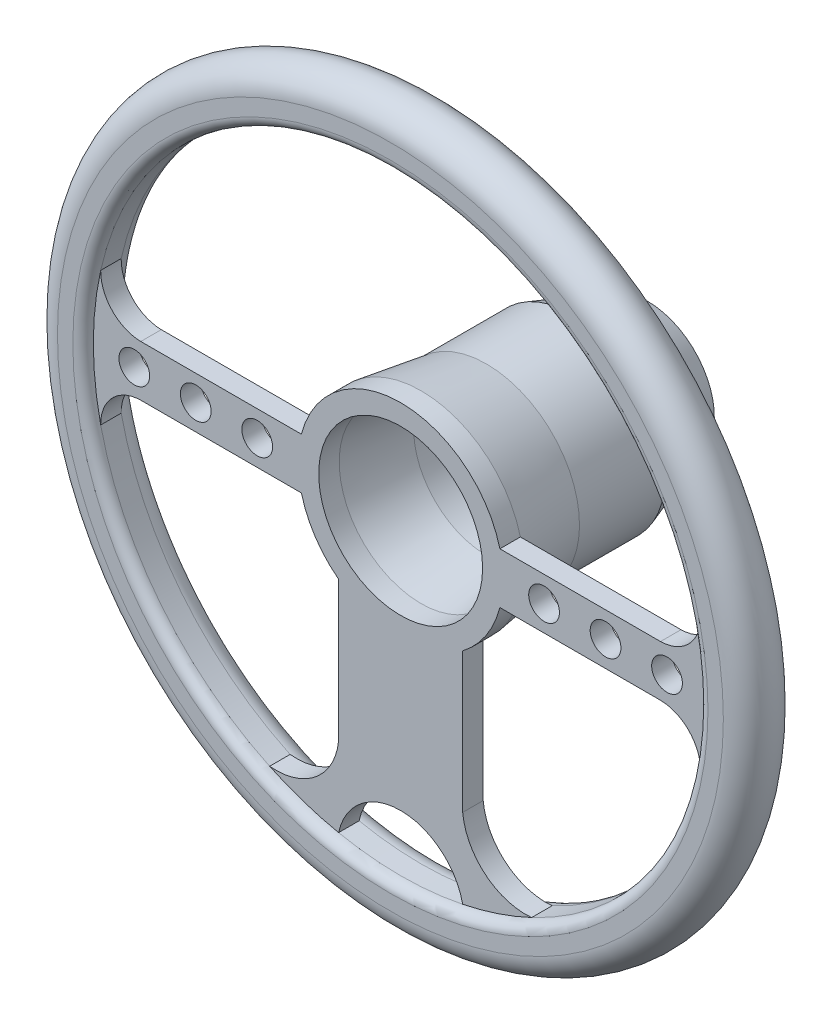
SolidWorks part; units mm, degrees
ref_plane "Płaszczyzna przednia" through (0, 0, 0) normal (0, 0, 1) x (1, 0, 0)
ref_plane "Płaszczyzna górna" through (0, 0, 0) normal (0, 1, 0) x (1, 0, 0)
ref_plane "Płaszczyzna prawa" through (0, 0, 0) normal (1, 0, 0) x (0, 0, -1)
sketch "Szkic1" plane through (0, 0, 0) normal (0, 0, 1) x (1, 0, 0)
  line L0 (0, 0) -> (0, -150)
  line L1 (0, 0) -> (-150, 0)
  line L2 (-48.4343, -12.4144) -> (-126.8213, -12.4144)
  line L3 (-48.4343, 12.4144) -> (-126.8213, 12.4144)
  line L4 (48.4343, 12.4144) -> (126.8213, 12.4144)
  line L5 (48.4343, -12.4144) -> (126.8213, -12.4144)
  line L7 (-30.2775, -39.7904) -> (-30.2775, -108.0825)
  line L8 (30.2775, -108.0825) -> (30.2775, -39.7904)
  circle A0 centre (0, 0) radius 175
  circle A1 centre (0, 0) radius 150
  circle A2 centre (0, 0) radius 50
  arc A3 (-146.3972, -32.6783) -> (-126.8213, -12.4144) centre (-126.4773, -32.3342) cw
  arc A4 (-146.3972, 32.6783) -> (-126.8213, 12.4144) centre (-126.4773, 32.3342) ccw
  arc A5 (146.3972, -32.6783) -> (126.8213, -12.4144) centre (126.4773, -32.3342) ccw
  arc A6 (146.3972, 32.6783) -> (126.8213, 12.4144) centre (126.4773, 32.3342) cw
  arc A7 (-30.2775, -146.9125) -> (30.2775, -146.9125) centre (0, -153.3685) cw
  arc A8 (-63.9487, -135.6856) -> (-30.2775, -108.0825) centre (-60.9146, -105.0485) ccw
  arc A9 (63.9487, -135.6856) -> (30.2775, -108.0825) centre (60.9146, -105.0485) cw
  circle A10 centre (-130, 0) radius 7.5
  circle A11 centre (-100, 0) radius 7.5
  circle A12 centre (-70, 0) radius 7.5
  circle A13 centre (70, 0) radius 7.5
  circle A14 centre (100, 0) radius 7.5
  circle A15 centre (130, 0) radius 7.5
  circle A16 centre (0, 0) radius 40
  dimension "D1" = 350
  dimension "D2" = 300
  dimension "D3" = 100
  dimension "D4" = 130
  dimension "D5" = 70
  dimension "D6" = 100
extrude "Dodanie-wyciągnięcie1" add sketch "Szkic1" along normal blind 25 contours A0 A1 | A12 L1 A11 A10 A1 A3 L2 A2 | A12 L1 A2 L3 A4 A1 A10 A11 | A16 L0 A2 L1 | A16 L1 A2 L0 | A8 A1 A7 L0 A2 L7 | A1 A9 L8 A2 L0 A7 | A1 A6 L4 A2 L5 A5 A14 A13 A15 region at (29.2843, -29.2843, 0) region at (-28.7658, -28.7658, 0) region at (19.4082, -94.4701, 0) region at (-19.4082, -94.4701, 0) region at (-104.4034, -8.2086, 0) region at (-104.4034, 8.2086, 0) region at (50.8053, -6.4075, 0) region at (-170.0503, 0, 0)
fillet "Zaokrąglenie1" 2 edges at (175, 0, 0) (175, 0, 25) type full round first side face at (76.4804, -59.1784, 0) second side face at (76.4804, -59.1784, 25) middle face at (175, 0, 25)
sketch "Szkic2" plane through (0, 0, 0) normal (1, 0, 0) x (0, 0, -1)
  line L0 (0, 0) -> (0, -150)
  line L1 (0, -150) -> (0, -146.9125) construction
  line L2 (0, -162.5) -> (0, 162.5) construction
  line L3 (0, -150) -> (-10, -150)
  line L4 (-10, -150) -> (-10, 0)
  line L5 (-10, 0) -> (0, 0)
  dimension "D1" = 10
revolve "Wycięcie-obrót1" cut sketch "Szkic2" angle 360 about L5
sketch "Szkic3" plane through (0, 0, 0) normal (1, 0, 0) x (0, 0, -1)
  line L0 (-25, 0) -> (-25, -150)
  line L1 (-25, 40) -> (-25, -40) construction
  line L2 (-25, 162.5) -> (-25, -162.5) construction
  line L3 (-25, -146.9125) -> (-25, -150) construction
  line L4 (-25, -150) -> (-20, -150)
  line L5 (-20, -150) -> (-20, 0)
  line L6 (-20, 0) -> (-25, 0)
  dimension "D1" = 5
revolve "Wycięcie-obrót2" cut sketch "Szkic3" angle 360 about L6
fillet "Zaokrąglenie4" radius 10 1 edges at (150, 0, 0)
fillet "Zaokrąglenie5" radius 5 1 edges at (150, 0, 25)
sketch "Szkic4" plane through (0, 0, 0) normal (1, 0, 0) x (0, 0, -1)
  line L0 (90.6185, 0) -> (100.4285, 0)
  line L1 (-10, 50) -> (21.9135, 45.3799)
  line L2 (-10, 12.4144) -> (-10, 50) construction
  line L3 (-10, 32.6783) -> (-10, 150) construction
  line L4 (21.9135, 45.3799) -> (63.9099, 45.3799)
  line L5 (63.9099, 45.3799) -> (100.4285, 32.6783)
  line L6 (100.4285, 32.6783) -> (100.4285, 0)
  line L7 (-10, 40) -> (21.9135, 35.5655)
  line L8 (-10, -40) -> (-10, 40) construction
  line L9 (21.9135, 35.5655) -> (63.9099, 35.5655)
  line L10 (63.9099, 35.5655) -> (90.6185, 27.0521)
  line L11 (100.4285, 0) -> (90.6185, 0)
  line L12 (90.6185, 0) -> (90.6185, 27.0521)
  line L13 (-10, 50) -> (-10, 40)
  line L14 (90.6185, 0) -> (11.5778, 0)
  line L15 (11.5778, 0) -> (0, 0)
  dimension "D1" = 9.81
revolve "Obrót3" add sketch "Szkic4" angle 360 about L14 region at (0, 13.5261, -91.8307)
sketch "Szkic5" plane through (0, 0, -90.6185) normal (0, 0, 1) x (1, 0, 0)
  circle A0 centre (0, 0) radius 12
  circle A1 centre (0, 20) radius 4
  circle A2 centre (20, 0) radius 4
  circle A3 centre (0, -20) radius 4
  circle A4 centre (-20, 0) radius 4
  dimension "D1" = 4
  dimension "D2" = 24
  dimension "D3" = 8
  dimension "D4" = 20
extrude "Wytnij-wyciągnięcie1" cut sketch "Szkic5" against normal blind 25
sketch "Szkic8" plane through (0, 0, -90.6185) normal (0, 0, 1) x (1, 0, 0)
sketch "Szkic9" plane through (0, 0, -90.6185) normal (0, 0, 1) x (1, 0, 0)
  circle A0 centre (0, 0) radius 12
  circle A1 centre (0, 20) radius 4
  circle A2 centre (20, 0) radius 4
  circle A3 centre (0, -20) radius 4
  circle A4 centre (-20, 0) radius 4
  circle A5 centre (0, 0) radius 27.0521
  dimension "D1" = 4
extrude "Dodanie-wyciągnięcie4" add sketch "Szkic9" along normal blind 45
sketch "Szkic10" plane through (0, 0, 0) normal (1, 0, 0) x (0, 0, -1)
  line L0 (0, 0) -> (45.6185, 0)
  line L1 (45.6185, 12) -> (45.6185, -12) construction
  line L2 (45.6185, 0) -> (45.6185, 12)
  line L3 (45.6185, 27.0521) -> (45.6185, -27.0521) construction
  line L4 (45.6185, 12) -> (57.6706, 12)
  line L5 (57.6706, 12) -> (57.6706, 27.0521)
  line L6 (57.6706, 27.0521) -> (90.6185, 27.0521)
  line L7 (90.6185, 27.0521) -> (90.6185, -27.0521) construction
  line L8 (90.6185, 27.0521) -> (63.9099, 35.5655)
  line L9 (63.9099, 35.5655) -> (63.9099, -35.5655) construction
  line L10 (63.9099, 35.5655) -> (45.6185, 35.5655)
  line L11 (45.6185, 35.5655) -> (45.6185, 12)
revolve "Obrót4" add sketch "Szkic10" angle 360 about L0 region at (0, 23.7828, -46.1265)
sketch "Szkic11" plane through (0, 0, -100.4285) normal (0, 0, -1) x (-1, 0, 0)
